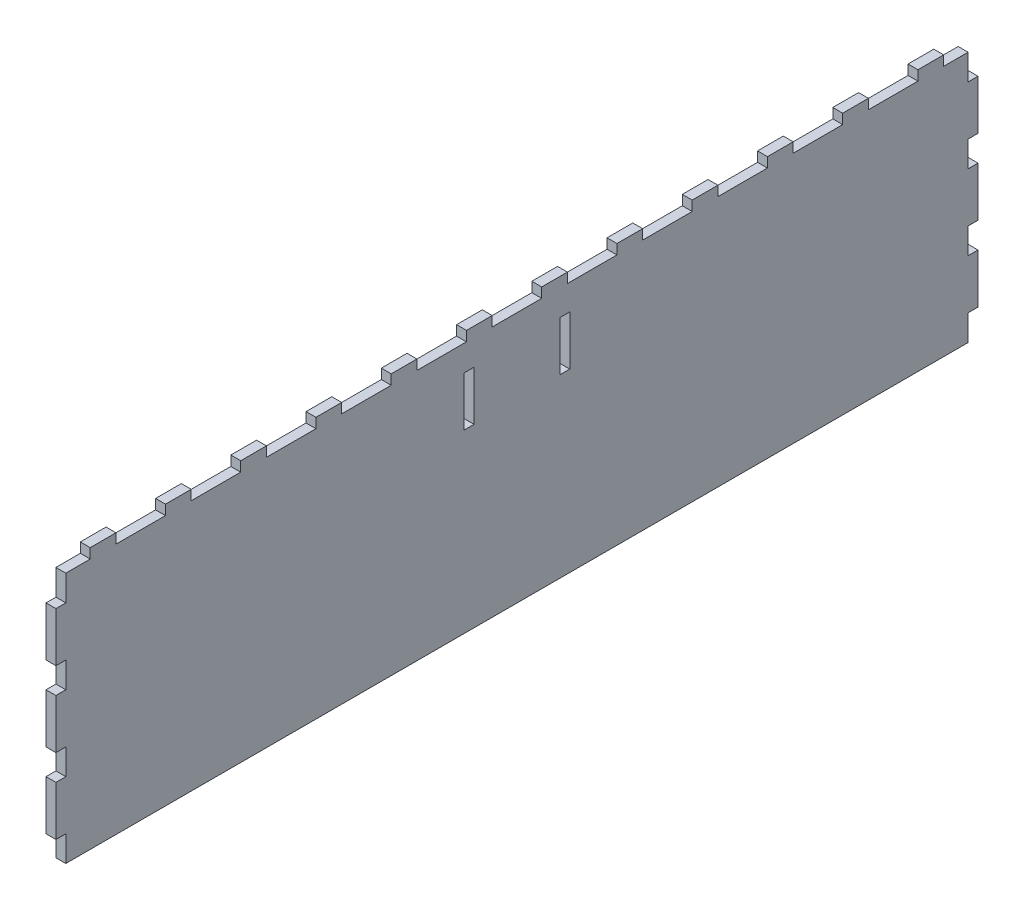
SolidWorks part; units mm, degrees
material "ENPH 253 Hardboard"
ref_plane "Front Plane" through (0, 0, 0) normal (0, 0, 1) x (1, 0, 0)
ref_plane "Top Plane" through (0, 0, 0) normal (0, 1, 0) x (1, 0, 0)
ref_plane "Right Plane" through (0, 0, 0) normal (1, 0, 0) x (0, 0, -1)
sketch "Sketch1" plane through (0, 0, 0) normal (1, 0, 0) x (0, 0, -1)
  line L1 (-139.7, 38.1) -> (139.7, 38.1)
  line L2 (-139.7, 38.1) -> (-139.7, -38.1)
  line L3 (-139.7, -38.1) -> (139.7, -38.1)
  line L4 (139.7, 38.1) -> (139.7, -38.1)
  line L5 (-139.7, 38.1) -> (139.7, -38.1) construction
  line L6 (-139.7, -38.1) -> (139.7, 38.1) construction
  point P0 (0, 0)
  dimension "D1" = 279.4
  dimension "D2" = 76.2
extrude "Boss-Extrude1" add sketch "Sketch1" against normal blind 3 contours L2 L3 L4 L1
sketch "Sketch3" plane through (-3, 0, 0) normal (-1, 0, 0) x (0, 0, 1)
  line L9 (-139.7, 38.1) -> (-136.7, 38.1)
  line L10 (-139.7, 38.1) -> (-139.7, 30.3)
  line L11 (-139.7, 30.3) -> (-136.7, 30.3)
  line L12 (-136.7, 38.1) -> (-136.7, 30.3)
  dimension "D9" = 7.8
  dimension "D10" = 3
extrude "Cut-Extrude1" cut sketch "Sketch3" against normal through all
pattern_linear "LPattern1" count 4 spacing 22.8 along (0, -1, 0) of "Cut-Extrude1"
mirror "Mirror1" about plane through (0, 0, 0) normal (0, 0, 1) of "LPattern1"
sketch "Sketch5" plane through (-3, 0, 0) normal (-1, 0, 0) x (0, 0, 1)
  line L1 (-16, 30.3) -> (-13, 30.3)
  line L2 (-16, 30.3) -> (-16, 15.3)
  line L3 (-16, 15.3) -> (-13, 15.3)
  line L4 (-13, 30.3) -> (-13, 15.3)
  line L5 (136.7, 38.1) -> (-136.7, 38.1) construction
  line L6 (0, -1.65) -> (0, 1.65) construction
  dimension "D1" = 13
  dimension "D2" = 3
  dimension "D3" = 7.8
  dimension "D4" = 15
extrude "Cut-Extrude3" cut sketch "Sketch5" against normal blind 10
mirror "Mirror2" about plane through (0, 0, 0) normal (0, 0, 1) of "Cut-Extrude3"
sketch "Sketch9" plane through (0, 38.1, 0) normal (0, 1, 0) x (1, 0, 0)
  line L0 (0, -136.7) -> (0, 136.7) construction
  line L1 (0, 129.3) -> (-3, 129.3)
  line L2 (0, 129.3) -> (0, 121.5)
  line L3 (0, 121.5) -> (-3, 121.5)
  line L4 (-3, 129.3) -> (-3, 121.5)
  line L5 (-3, -136.7) -> (-3, 136.7) construction
  line L6 (0, 136.7) -> (-3, 136.7) construction
  point P10 (-1.5, 129.3)
  dimension "D1" = 7.4
  dimension "D2" = 7.8
extrude "Boss-Extrude2" add sketch "Sketch9" along normal blind 3
pattern_linear "LPattern4" count 12 spacing 22.8 along (0, 0, 1) of "Boss-Extrude2"
